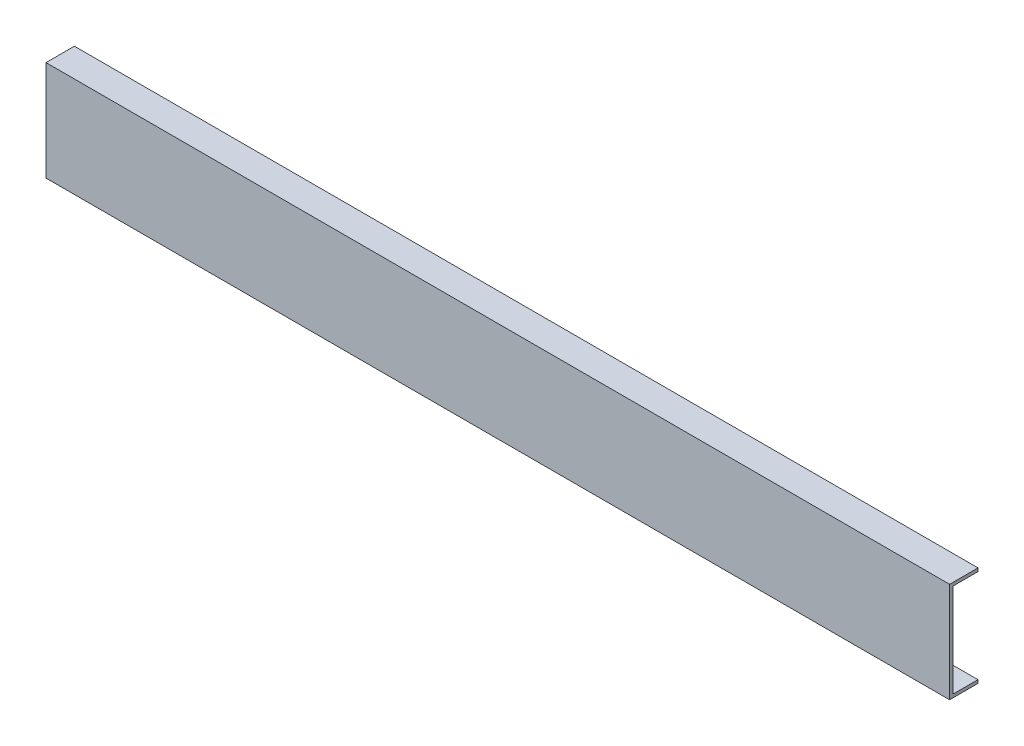
SolidWorks part; units mm, degrees
ref_plane "Front Plane" through (0, 0, 0) normal (0, 0, 1) x (1, 0, 0)
ref_plane "Top Plane" through (0, 0, 0) normal (0, 1, 0) x (1, 0, 0)
ref_plane "Right Plane" through (0, 0, 0) normal (1, 0, 0) x (0, 0, -1)
sketch "Sketch2" plane through (0, 0, 0) normal (0, 0, 1) x (1, 0, 0)
  line L1 (0, 0) -> (711.2, 0)
  line L2 (0, 0) -> (0, 78.74)
  line L3 (0, 78.74) -> (711.2, 78.74)
  line L4 (711.2, 0) -> (711.2, 78.74)
  dimension "D1" = 78.74
  dimension "D2" = 711.2
extrude "Boss-Extrude1" add sketch "Sketch2" along normal blind 22.352
sketch "Sketch3" plane through (711.2, 0, 0) normal (1, 0, 0) x (0, 0, -1)
  line L0 (0, 0) -> (0, 78.74) construction
  line L1 (0, 76.2) -> (-19.812, 76.2)
  line L2 (0, 76.2) -> (0, 2.54)
  line L3 (0, 2.54) -> (-19.812, 2.54)
  line L4 (-19.812, 76.2) -> (-19.812, 2.54)
  line L5 (-22.352, 0) -> (-22.352, 78.74) construction
  line L6 (-22.352, 78.74) -> (0, 78.74) construction
  line L7 (-22.352, 0) -> (0, 0) construction
  dimension "D1" = 2.54
  dimension "D2" = 2.54
  dimension "D3" = 2.54
extrude "Cut-Extrude1" cut sketch "Sketch3" against normal through all
